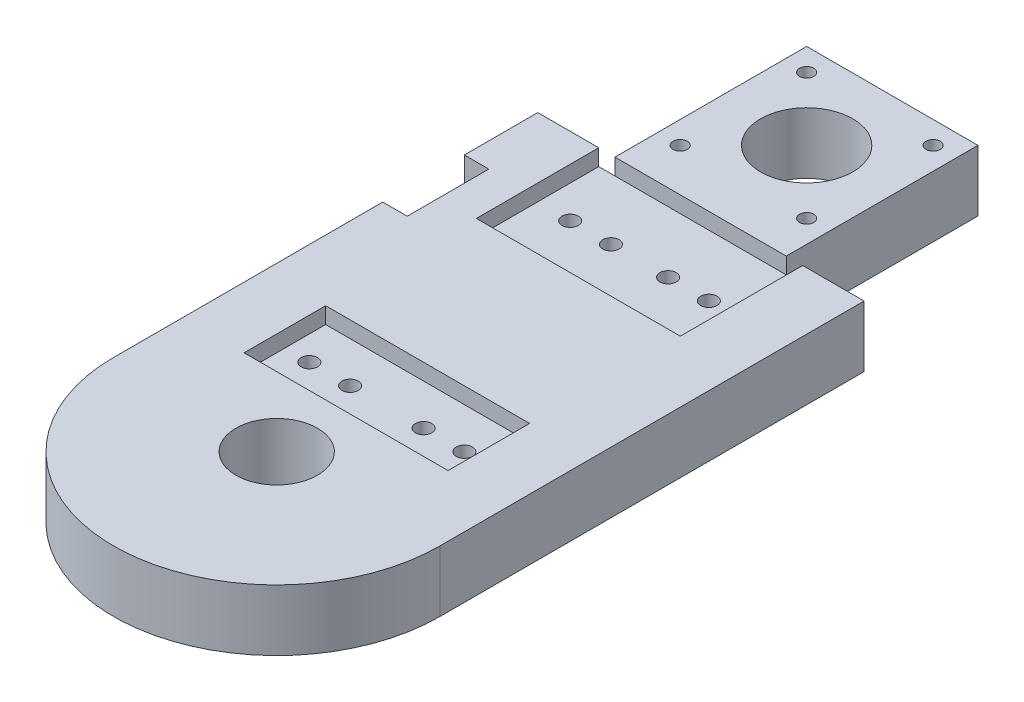
SolidWorks part; units mm, degrees
ref_plane "Ebene vorne" through (0, 0, 0) normal (0, 0, 1) x (1, 0, 0)
ref_plane "Ebene oben" through (0, 0, 0) normal (0, 1, 0) x (1, 0, 0)
ref_plane "Ebene rechts" through (0, 0, 0) normal (1, 0, 0) x (0, 0, -1)
sketch "Skizze1" plane through (0, 0, 0) normal (0, 1, 0) x (1, 0, 0)
  line L0 (-25.9794, -40) -> (25.9794, -40) construction
  line L1 (-40, 0) -> (40, 0)
  line L2 (-40, 0) -> (-40, 104)
  line L4 (40, 0) -> (40, 104)
  line L5 (-40, 0) -> (40, 104) construction
  line L6 (-40, 104) -> (40, 0) construction
  line L9 (-40, 104) -> (-40, 78)
  line L12 (-40, 104) -> (40, 104)
  line L13 (-21.0848, 151) -> (20.9152, 109) construction
  line L21 (-21.0848, 104) -> (20.9152, 104)
  line L22 (-21.0848, 104) -> (-21.0848, 151)
  line L23 (-21.0848, 151) -> (20.9152, 151)
  line L24 (20.9152, 104) -> (20.9152, 151)
  line L25 (20.9152, 151) -> (-21.0848, 109) construction
  circle A0 centre (0, 0) radius 40
  circle A2 centre (-0.0848, 130) radius 11.3
  circle A3 centre (-15.5848, 145.5) radius 1.75
  circle A4 centre (15.4152, 145.5) radius 1.75
  circle A5 centre (15.4152, 114.5) radius 1.75
  circle A6 centre (-15.5848, 114.5) radius 1.75
  point P7 (0, 52)
  point P11 (0, -40)
  point P31 (-0.0848, 130)
  dimension "D1" = 80
  dimension "D5" = 144
  dimension "D4" = 42
  dimension "D6" = 4
  dimension "D2" = 42
  dimension "D3" = 5
extrude "Aufsatz-Linear austragen1" add sketch "Skizze1" along normal blind 15
sketch "Skizze5" plane through (0, 15, 0) normal (0, 1, 0) x (1, 0, 0)
  line L0 (40, 0) -> (40, 104) construction
  line L1 (-25, 74) -> (40, 74)
  line L2 (-25, 74) -> (-25, 37)
  line L3 (-25, 37) -> (40, 37)
  line L4 (40, 74) -> (40, 37)
  line L5 (-25, 74) -> (40, 37) construction
  line L6 (-25, 37) -> (40, 74) construction
  line L7 (0, 0) -> (0, 27) construction
  line L8 (-25, 37) -> (40, 37)
  line L12 (20.9152, 104) -> (40, 104) construction
  line L14 (-25, 17) -> (25, 17)
  line L15 (-25, 17) -> (-25, 37)
  line L16 (-25, 37) -> (25, 37)
  line L17 (25, 17) -> (25, 37)
  line L18 (-25, 17) -> (25, 37) construction
  line L19 (-25, 37) -> (25, 17) construction
  point P4 (7.5, 55.5)
  point P13 (0, 27)
  dimension "D1" = 20
  dimension "D2" = 37
  dimension "D3" = 50
  dimension "D4" = 30
extrude "Schnitt-Linear austragen3" cut sketch "Skizze5" against normal blind 4 contours L14 L17 L3 L16 L15 region at (0, 15, -27)
sketch "Skizze6" plane through (0, 11, 0) normal (0, 1, 0) x (1, 0, 0)
  line L0 (-25, 27) -> (25, 27) construction
  line L3 (0, 27) -> (0, 3.2798) construction
  line L5 (25, 17) -> (25, 37) construction
  circle A0 centre (9, 27) radius 2
  circle A1 centre (-9, 27) radius 2
  circle A2 centre (19, 27) radius 2
  circle A3 centre (-19, 27) radius 2
  dimension "D2" = 4
  dimension "D3" = 4
  dimension "D4" = 10
extrude "Schnitt-Linear austragen4" cut sketch "Skizze6" against normal blind 11
sketch "Skizze8" plane through (0, 0, 0) normal (0, -1, 0) x (1, 0, 0)
  circle A0 centre (0, 0) radius 20
  circle A1 centre (0, 0) radius 32.5
  circle A2 centre (0, 0) radius 26.25
  dimension "D1" = 40
  dimension "D2" = 65
  dimension "D3" = 52.5
extrude "Schnitt-Linear austragen5" cut sketch "Skizze8" against normal blind 4 contours A1 A2 region at (-31.5808, 0, 0)
sketch "Skizze10" plane through (0, 0, 0) normal (0, -1, 0) x (1, 0, 0)
  circle A0 centre (0, 0) radius 10
sketch "Skizze11" plane through (0, 0, 0) normal (0, -1, 0) x (1, 0, 0)
  circle A0 centre (9, -27) radius 3.5
  circle A1 centre (19, -27) radius 3.5
  circle A2 centre (-19, -27) radius 3.5
  circle A3 centre (-9, -27) radius 3.5
  dimension "D1" = 7
  dimension "D2" = 7
extrude "Schnitt-Linear austragen6" cut sketch "Skizze11" against normal offset from surface (8 mm away) 8 up to face at (0, 0, -26.25)
sketch "Skizze14" plane through (0, 15, 0) normal (0, 1, 0) x (1, 0, 0)
  line L0 (-40, 104) -> (-40, 86) construction
  line L1 (-40, 0) -> (-40, 104) construction
  line L2 (-40, 104) -> (-21.0848, 104) construction
  line L4 (-40, 86) -> (-34, 86)
  line L5 (-40, 86) -> (-40, 66)
  line L6 (-40, 66) -> (-34, 66)
  line L7 (-34, 86) -> (-34, 66)
  line L8 (-40, 86) -> (-34, 66) construction
  line L9 (-40, 66) -> (-34, 86) construction
  point P9 (-37, 76)
  dimension "D1" = 20
  dimension "D2" = 18
  dimension "D3" = 6
extrude "Schnitt-Linear austragen11" cut sketch "Skizze14" against normal blind 15 contours L5 L4 L7 L6
sketch "Skizze15" plane through (-34, 0, 0) normal (-1, 0, 0) x (0, 0, 1)
  circle A1 centre (-80.5, 7.5) radius 1.25
  circle A2 centre (-71, 7.5) radius 1.25
  circle A3 centre (-71, 7.5) radius 1.25 construction
  circle A4 centre (-80.5, 7.5) radius 1.25 construction
extrude "Schnitt-Linear austragen12" cut sketch "Skizze15" against normal blind 6
extrude "Cut-Extrude1" cut sketch "Skizze10" against normal blind 15
sketch "Skizze19" plane through (0, 15, 0) normal (0, 1, 0) x (1, 0, 0)
  line L0 (0, 0) -> (-0.0848, 130) construction
  line L1 (20.9152, 104) -> (40, 104) construction
  line L2 (-25.058, 74) -> (24.942, 74)
  line L3 (-25.058, 74) -> (-25.058, 104)
  line L4 (-25.058, 104) -> (24.942, 104)
  line L5 (24.942, 74) -> (24.942, 104)
  line L6 (-25.058, 74) -> (24.942, 104) construction
  line L7 (-25.058, 104) -> (24.942, 74) construction
  point P4 (-0.058, 89)
  dimension "D1" = 50
  dimension "D2" = 30
extrude "Schnitt-Linear austragen15" cut sketch "Skizze19" against normal blind 4
sketch "Skizze20" plane through (0, 11, 0) normal (0, 1, 0) x (1, 0, 0)
  line L0 (-25.058, 89) -> (24.942, 89) construction
  line L1 (-25.058, 104) -> (-25.058, 74) construction
  line L2 (24.942, 74) -> (24.942, 104) construction
sketch "Skizze21" plane through (0, 11, 0) normal (0, 1, 0) x (1, 0, 0)
  line L0 (-25.058, 89) -> (24.942, 89) construction
  line L1 (-0.058, 89) -> (-0.058, 95.2298) construction
  circle A0 centre (16.942, 89) radius 2
  circle A1 centre (6.942, 89) radius 2
  circle A2 centre (-17.058, 89) radius 2
  circle A3 centre (-7.058, 89) radius 2
  dimension "D1" = 8
  dimension "D2" = 10
extrude "Schnitt-Linear austragen16" cut sketch "Skizze21" against normal blind 11
sketch "Skizze22" plane through (0, 0, 0) normal (0, -1, 0) x (1, 0, 0)
  line L0 (-0.058, -89) -> (-0.058, -83.762) construction
  line L1 (-25.058, -89) -> (24.942, -89) construction
  circle A0 centre (-17.058, -89) radius 4.2
  circle A1 centre (-7.058, -89) radius 4.2
  circle A2 centre (6.942, -89) radius 4.2
  circle A3 centre (16.942, -89) radius 4.2
extrude "Schnitt-Linear austragen17" cut sketch "Skizze22" against normal blind 4
sketch "Skizze23" plane through (0, 0, 0) normal (0, -1, 0) x (1, 0, 0)
  circle A0 centre (-15.5848, -114.5) radius 3
  circle A1 centre (-0.0848, -130) radius 11.3
  circle A2 centre (15.4152, -114.5) radius 3
  circle A3 centre (15.4152, -145.5) radius 3
  circle A4 centre (-15.5848, -145.5) radius 3
  point P15 (-0.0848, -130)
  dimension "D1" = 4
extrude "Schnitt-Linear austragen18" cut sketch "Skizze23" against normal blind 4
